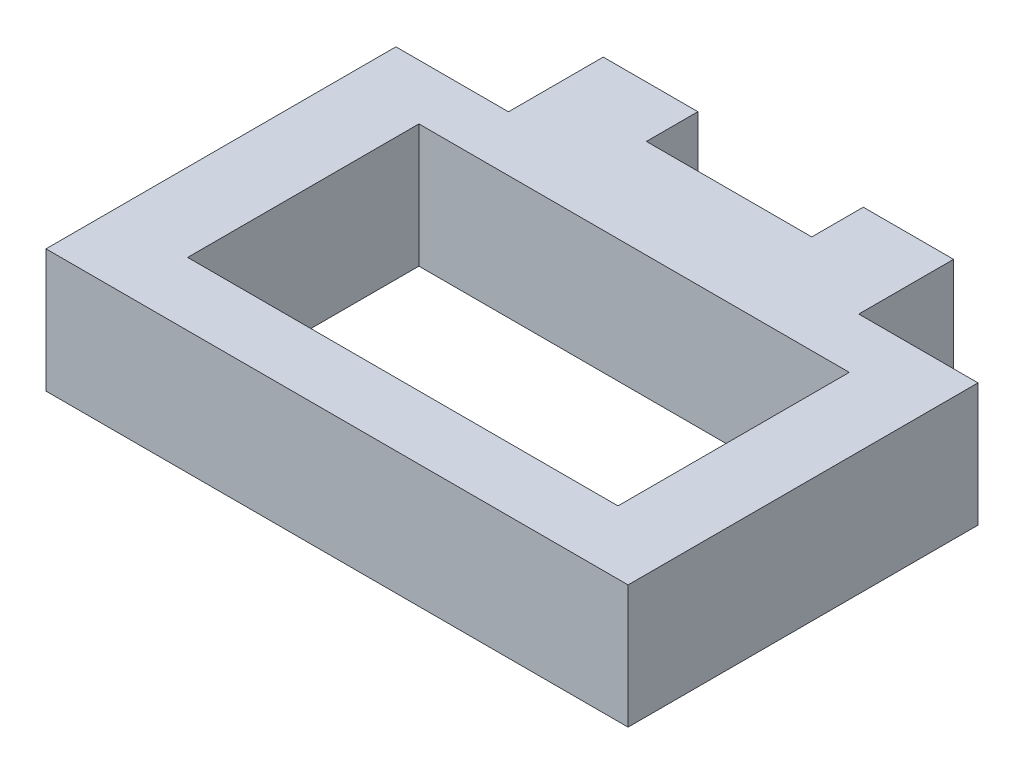
SolidWorks part; units mm, degrees
ref_plane "Front Plane" through (0, 0, 0) normal (0, 0, 1) x (1, 0, 0)
ref_plane "Top Plane" through (0, 0, 0) normal (0, 1, 0) x (1, 0, 0)
ref_plane "Right Plane" through (0, 0, 0) normal (1, 0, 0) x (0, 0, -1)
sketch "Sketch1" plane through (0, 0, 0) normal (0, 1, 0) x (1, 0, 0)
  line L0 (23.2084, 35.617) -> (23.2084, 32.9001)
  line L1 (16.4084, 27.7029) -> (39.1084, 27.7029)
  line L2 (16.4084, 27.7029) -> (16.4084, 15.5029)
  line L3 (16.4084, 15.5029) -> (39.1084, 15.5029)
  line L4 (39.1084, 27.7029) -> (39.1084, 15.5029)
  line L5 (12.281, 30.617) -> (42.9837, 30.617)
  line L6 (12.281, 30.617) -> (12.281, 12.1599)
  line L7 (12.281, 12.1599) -> (42.9837, 12.1599)
  line L8 (42.9837, 30.617) -> (42.9837, 12.1599)
  line L9 (31.8568, 35.617) -> (31.8949, 35.617)
  line L10 (18.2174, 35.617) -> (18.2174, 30.617)
  line L11 (18.2174, 30.617) -> (36.6953, 30.617)
  line L12 (36.6953, 35.617) -> (36.6953, 30.617)
  line L13 (23.2084, 32.9001) -> (31.933, 32.9001)
  line L14 (31.933, 32.9001) -> (31.933, 35.617)
  line L15 (18.2174, 35.617) -> (23.2084, 35.617)
  line L16 (31.933, 35.617) -> (36.6953, 35.617)
  dimension "D1" = 22.7
  dimension "D2" = 12.2
  dimension "D3" = 5
extrude "Boss-Extrude5" add sketch "Sketch1" along normal blind 6.5 contours L8 L5 L6 L7 L1 L4 L3 L2 | L16 L14 L13 L0 L15 L10 L5 L12 region at (27.4169, 0, -32.723) region at (27.4564, 0, -30.2587)
